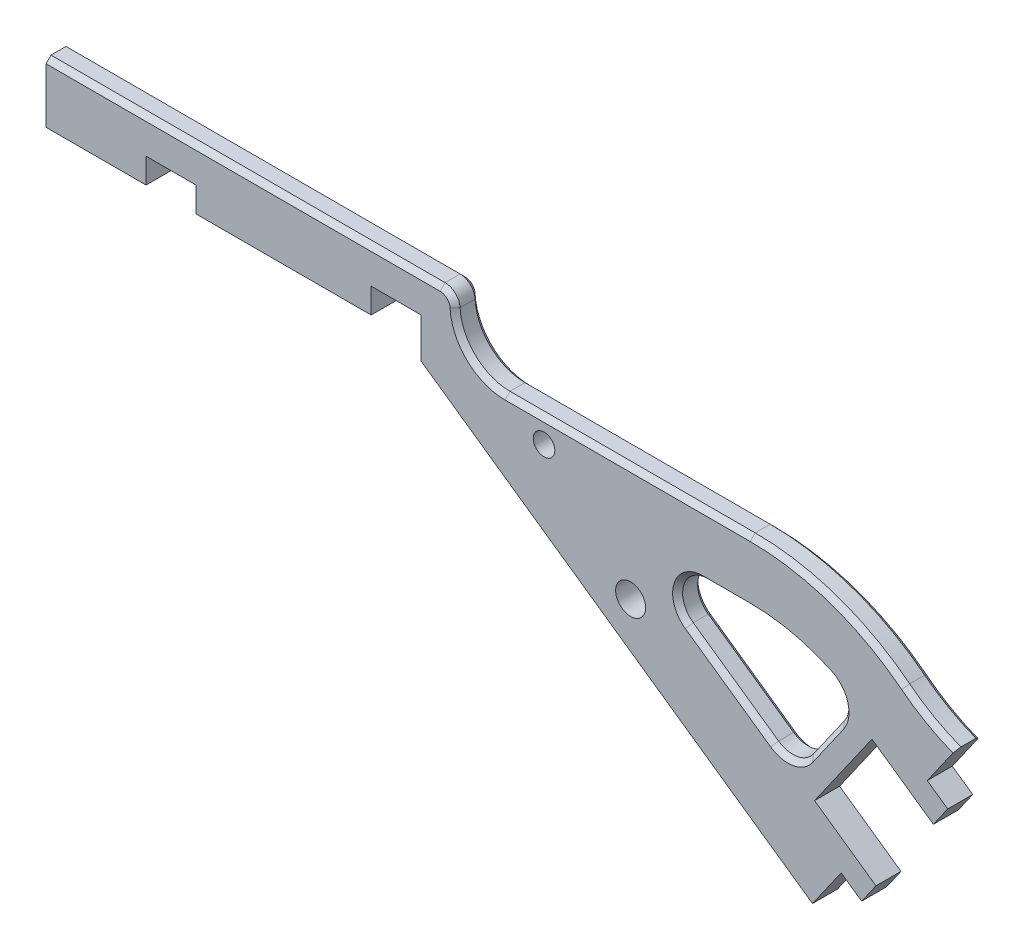
SolidWorks part; units mm, degrees
material "6061-T4 (SS)"
ref_plane "Front Plane" through (0, 0, 0) normal (0, 0, 1) x (1, 0, 0)
ref_plane "Top Plane" through (0, 0, 0) normal (0, 1, 0) x (1, 0, 0)
ref_plane "Right Plane" through (0, 0, 0) normal (1, 0, 0) x (0, 0, -1)
sketch "Sketch1" plane through (0, 0, 0) normal (0, 0, 1) x (1, 0, 0)
  line L1 (3.22, -18) -> (20, -18)
  line L3 (23.22, -13) -> (30, -13)
  line L5 (33.22, -18) -> (65, -18)
  line L7 (68.22, -13) -> (78.2164, -13)
  line L8 (78.2164, -13) -> (78.2164, -21)
  line L9 (78.2164, -21) -> (156.4454, -75.7765)
  line L10 (3.22, -6) -> (82, -6)
  line L11 (94.9824, -18.3242) -> (143.9824, -18.3242)
  line L12 (185.1243, -34.8189) -> (179.3885, -43.0105)
  line L13 (179.3885, -43.0105) -> (183.4843, -45.8784)
  line L14 (183.4843, -45.8784) -> (180.6164, -49.9741)
  line L15 (156.4454, -75.7765) -> (162.1812, -67.585)
  line L16 (162.1812, -67.585) -> (166.277, -70.4529)
  line L17 (166.277, -70.4529) -> (169.1448, -66.3572)
  line L18 (169.1448, -66.3572) -> (156.8576, -57.7535)
  line L19 (156.8576, -57.7535) -> (168.3291, -41.3705)
  line L20 (168.3291, -41.3705) -> (180.6164, -49.9741)
  line L21 (148.666, -52.0177) -> (131.6145, -40.0782)
  line L22 (134.4824, -30.9824) -> (143.9824, -30.9824)
  line L23 (161.8381, -41.9234) -> (155.6297, -50.7899)
  line L24 (33.22, -13) -> (30, -13)
  line L25 (68.22, -13) -> (68.22, -18)
  line L26 (68.22, -18) -> (65, -18)
  line L27 (116.88, -41.25) -> (120.09, -41.25)
  line L28 (23.22, -13) -> (23.22, -18)
  line L30 (33.22, -18) -> (33.22, -13)
  line L31 (20, -18) -> (23.22, -18)
  line L32 (3.22, -18) -> (3.22, -6)
  arc A0 (82, -6) -> (84.9959, -8.844) centre (82, -9) cw
  arc A1 (84.9959, -8.844) -> (94.9824, -18.3242) centre (94.9824, -8.3242) ccw
  arc A4 (174.889, -29.0205) -> (185.1243, -34.8189) centre (199.0703, 1.7308) ccw
  arc A5 (143.9824, -18.3242) -> (174.889, -29.0205) centre (143.9824, -68.3242) cw
  arc A6 (131.6145, -40.0782) -> (134.4824, -30.9824) centre (134.4824, -35.9824) cw
  arc A7 (143.9824, -30.9824) -> (159.8696, -34.5306) centre (143.9824, -68.3242) cw
  arc A8 (159.8696, -34.5306) -> (161.8381, -41.9234) centre (157.7423, -39.0555) cw
  arc A9 (155.6297, -50.7899) -> (148.666, -52.0177) centre (151.5339, -47.922) cw
  circle A11 centre (120.09, -41.25) radius 3
  dimension "D11" = 3
  dimension "D12" = 10
  dimension "D13" = 49
  dimension "D17" = 95.5
  dimension "D18" = 39.12
  dimension "D19" = 50
  dimension "D21" = 15
  dimension "D22" = 5
  dimension "D5" = 6
  dimension "D3" = 8
  dimension "D4" = 3.21
  dimension "D8" = 145
  dimension "D9" = 50
  dimension "D14" = 10
  dimension "D15" = 5
  dimension "D16" = 20
  dimension "D20" = 15
  dimension "D23" = 9.5
  dimension "D24" = 5
  dimension "D27" = 35.25
  dimension "D28" = 3.22
extrude "Boss-Extrude1" add sketch "Sketch1" along normal blind 5 contours A5 L11 A1 A0 L10 L1 L3 L5 L7 L8 L9 L15 L16 L17 L18 L19 L20 L14 L13 L12 A4 L23 A9 L21 A6 L22 A7 A8 region at (111.4584, -31.0498, 0)
chamfer "Chamfer1" distance 1 angle 45 26 edges at (162.574, -37.7689, 0) (152.1217, -31.8802, 0) (158.7339, -46.3566, 0) (139.2324, -30.9824, 0) (152.4022, -52.846, 0) (129.7138, -34.4789, 0) (140.1403, -46.0479, 0) (158.7339, -46.3566, 5) (162.574, -37.7689, 5) (152.4022, -52.846, 5) (152.1217, -31.8802, 5) (140.1403, -46.0479, 5) (139.2324, -30.9824, 5) (129.7138, -34.4789, 5) (179.7874, -32.3066, 0) (160.335, -21.0739, 0) (119.4824, -18.3242, 0) (88.0976, -15.5767, 0) (84.0654, -6.8242, 0) (42.61, -6, 0) (179.7874, -32.3066, 5) (160.335, -21.0739, 5) (119.4824, -18.3242, 5) (88.0976, -15.5767, 5) (84.0654, -6.8242, 5) (42.61, -6, 5)
sketch "Sketch2" plane through (0, 0, 0) normal (0, 0, -1) x (-1, 0, 0)
  circle A0 centre (-102.7824, -23.1151) radius 2.153
  point P2 (-102.7824, -23.1151)
extrude "Cut-Extrude1" cut sketch "Sketch2" against normal through all
